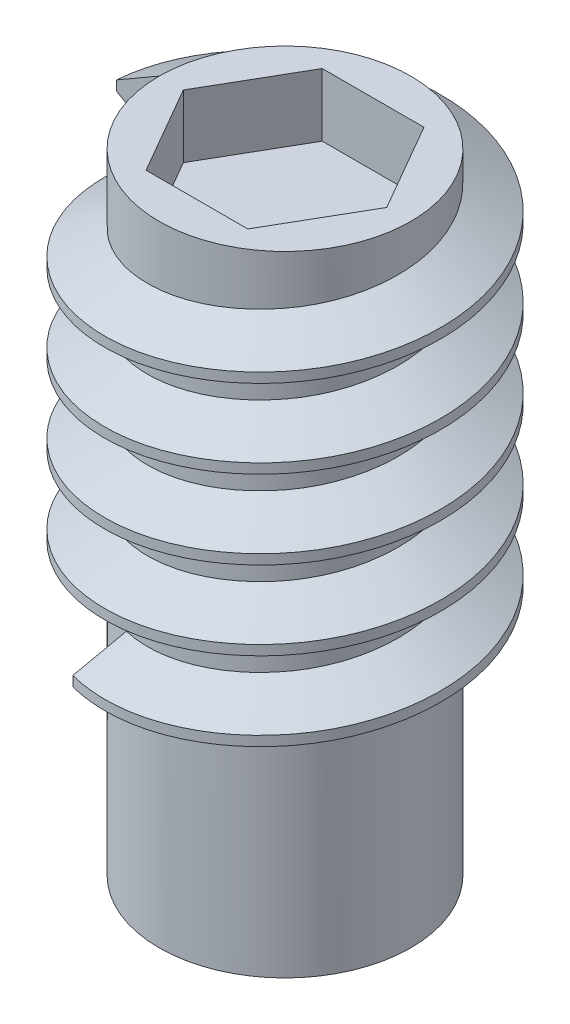
SolidWorks part; units mm, degrees
material "Plain Carbon Steel"
ref_plane "Front Plane" through (0, 0, 0) normal (0, 0, 1) x (1, 0, 0)
ref_plane "Top Plane" through (0, 0, 0) normal (0, 1, 0) x (1, 0, 0)
ref_plane "Right Plane" through (0, 0, 0) normal (1, 0, 0) x (0, 0, -1)
sketch "Sketch1" plane through (0, 0, 0) normal (0, 1, 0) x (1, 0, 0)
  circle A0 centre (0, 0) radius 1.27
  dimension "D1" = 2.54
extrude "Boss-Extrude1" add sketch "Sketch1" along normal blind 6.35
thread "Thread1" pitch 0.7937 method extrude profile "Thread Profile1" start angle 0, offset 0, length 3.81, pitch 0.7937, diameter 2.54
ref_plane "Plane1" through (-1.27, 6.35, 0) normal (0, 0, 1) x (-1, 0, 0)
sketch "Thread Profile1" plane through (-1.27, 6.35, 0) normal (0, 0, 1) x (-1, 0, 0)
  line L0 (0, 0) -> (0, 0.7937) construction
  line L1 (0, 0) -> (0.4296, 0.248)
  line L2 (0.4296, 0.248) -> (0.4296, 0.3473)
  line L3 (0.4296, 0.3473) -> (0, 0.5953)
  line L4 (0.4296, 0.2977) -> (0, 0.2977) construction
  line L11 (0, 0) -> (0, 0.5953)
  point P2 (0, 0)
  dimension "Pitch" = 0.7937
  dimension "Profile_Angle" = 60
  dimension "Profile_Land" = 0.0992
  dimension "Profile_Height" = 0.4296
sketch "Sketch6" plane through (0, 6.35, 0) normal (0, 1, 0) x (1, 0, 0)
  line L1 (-1.0265, 0) -> (-0.5133, -0.889)
  line L2 (-0.5133, -0.889) -> (0.5133, -0.889)
  line L3 (0.5133, -0.889) -> (1.0265, 0)
  line L4 (1.0265, 0) -> (0.5133, 0.889)
  line L5 (0.5133, 0.889) -> (-0.5133, 0.889)
  line L6 (-0.5133, 0.889) -> (-1.0265, 0)
  circle A0 centre (0, 0) radius 0.889 construction
  dimension "D1" = 1.778
extrude "Cut-Extrude1" cut sketch "Sketch6" against normal blind 0.635
